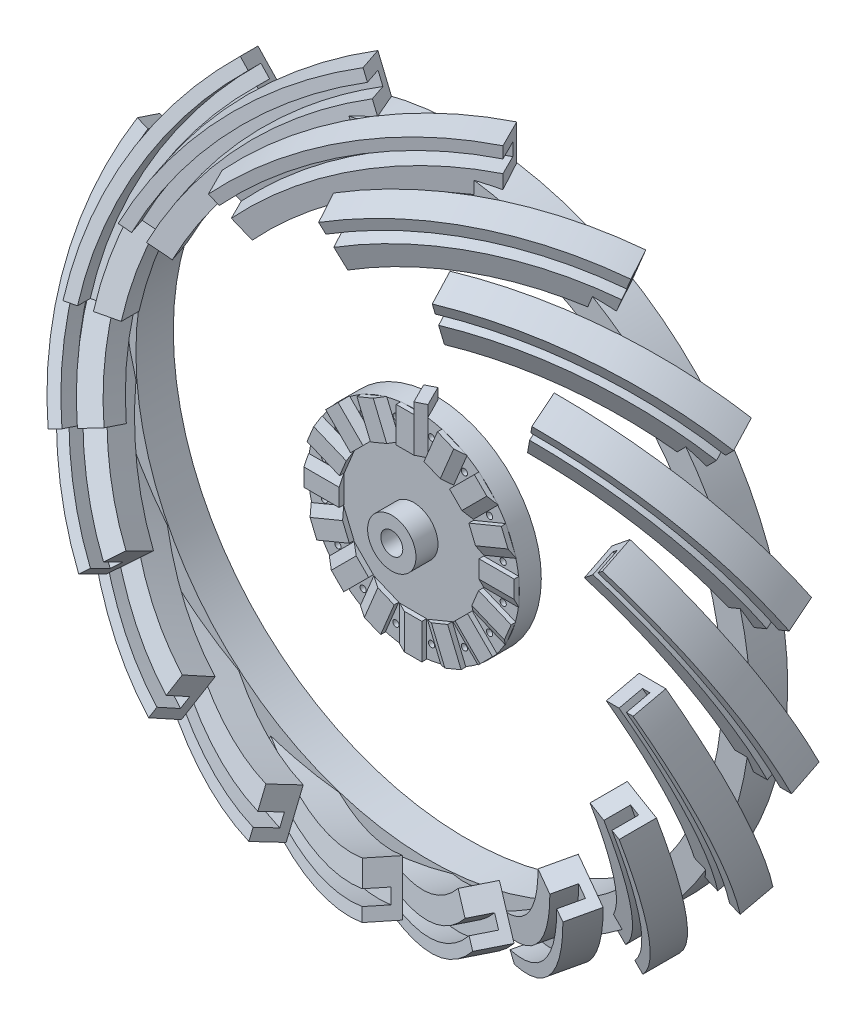
SolidWorks part; units mm, degrees
ref_plane "Front" through (0, 0, 0) normal (0, 0, 1) x (1, 0, 0)
ref_plane "Top" through (0, 0, 0) normal (0, 1, 0) x (1, 0, 0)
ref_plane "Right" through (0, 0, 0) normal (1, 0, 0) x (0, 0, -1)
sketch "Sketch1" plane through (0, 0, 0) normal (0, 0, 1) x (1, 0, 0)
  circle A0 centre (0, 0) radius 24
extrude "Extrude1" add sketch "Sketch1" along normal blind 5
sketch "Sketch2" plane through (0, 0, 5) normal (0, 0, 1) x (1, 0, 0)
  circle A0 centre (0, 0) radius 5.5
extrude "Extrude2" add sketch "Sketch2" along normal blind 5
sketch "Sketch3" plane through (0, 0, 10) normal (0, 0, 1) x (1, 0, 0)
  circle A0 centre (0, 0) radius 2.5
extrude "Cut-Extrude1" cut sketch "Sketch3" against normal through all
sketch "Sketch4" plane through (0, 0, 5) normal (0, 0, 1) x (1, 0, 0)
  circle A0 centre (0, 20.73) radius 0.7
  circle A1 centre (0, -20.73) radius 0.7
  circle A2 centre (20.73, 0) radius 0.7
  circle A3 centre (-20.73, 0) radius 0.7
  circle A4 centre (-14.658, 14.658) radius 0.7
  circle A5 centre (14.658, 14.658) radius 0.7
  circle A6 centre (14.658, -14.658) radius 0.7
  circle A7 centre (-14.658, -14.658) radius 0.7
  circle A8 centre (19.152, 7.933) radius 0.7
  circle A9 centre (7.933, 19.152) radius 0.7
  circle A10 centre (19.152, -7.933) radius 0.7
  circle A11 centre (7.933, -19.152) radius 0.7
  circle A12 centre (-7.933, 19.152) radius 0.7
  circle A13 centre (-19.152, 7.933) radius 0.7
  circle A14 centre (-19.152, -7.933) radius 0.7
  circle A15 centre (-7.933, -19.152) radius 0.7
  circle A16 centre (20.331, 4.044) radius 0.7
  circle A17 centre (20.331, -4.044) radius 0.7
  circle A18 centre (4.044, -20.331) radius 0.7
  circle A19 centre (-4.044, -20.331) radius 0.7
  circle A20 centre (4.044, 20.331) radius 0.7
  circle A21 centre (-4.044, 20.331) radius 0.6677
  circle A22 centre (-20.331, 4.044) radius 0.7
  circle A23 centre (-20.331, -4.044) radius 0.7
  circle A24 centre (17.236, 11.516) radius 0.7
  circle A25 centre (11.516, 17.236) radius 0.7
  circle A26 centre (17.236, -11.516) radius 0.7
  circle A27 centre (11.516, -17.236) radius 0.7
  circle A28 centre (-11.516, -17.236) radius 0.7
  circle A29 centre (-17.236, -11.516) radius 0.7
  circle A30 centre (-17.236, 11.516) radius 0.7
  circle A31 centre (-11.516, 17.236) radius 0.7
  circle A32 centre (0, 17.555) radius 0.7
  circle A33 centre (17.555, 0) radius 0.7
  circle A34 centre (0, -17.555) radius 0.7
  circle A35 centre (-17.555, 0) radius 0.7
  circle A36 centre (-12.413, 12.413) radius 0.7
  circle A37 centre (12.413, 12.413) radius 0.7
  circle A38 centre (12.413, -12.413) radius 0.7
  circle A39 centre (-12.413, -12.413) radius 0.7
  circle A40 centre (-16.218, 6.718) radius 0.7
  circle A41 centre (16.218, 6.718) radius 0.7
  circle A42 centre (16.218, -6.718) radius 0.7
  circle A43 centre (-16.218, -6.718) radius 0.7
  circle A44 centre (6.718, 16.218) radius 0.7
  circle A45 centre (6.718, -16.218) radius 0.7
  circle A46 centre (-6.718, -16.218) radius 0.7
  circle A47 centre (-6.718, 16.218) radius 0.7
extrude "Cut-Extrude2" cut sketch "Sketch4" against normal through all
sketch "Sketch5" plane through (0, 0, 5) normal (0, 0, 1) x (1, 0, 0)
  line L0 (0, 25.4) -> (0, 11.1125) construction
  line L1 (3.2361, 25.4) -> (3.2361, 11.1125) construction
  line L2 (-2.9131, 25.4) -> (-2.9131, 11.1125) construction
  line L3 (-6.35, 15.905) -> (6.35, 15.905) construction
  line L4 (-6.35, 23.905) -> (6.35, 23.905) construction
  line L5 (-2.9131, 23.905) -> (3.2361, 23.905)
  line L6 (3.2361, 23.905) -> (3.2361, 15.905)
  line L7 (3.2361, 15.905) -> (-2.9131, 15.905)
  line L8 (-2.9131, 15.905) -> (-2.9131, 23.905)
  line L9 (-7.933, -19.152) -> (7.933, 19.152) construction
  line L10 (6.0866, 14.6943) -> (32.5356, 3.7388) construction
  line L11 (3.3952, 15.8091) -> (7.7143, 26.2363) construction
  line L12 (9.0763, 13.4559) -> (14.7806, 27.2273) construction
  line L13 (7.5216, 22.759) -> (13.5204, 20.2742) construction
  line L14 (3.3952, 15.8091) -> (9.0763, 13.4559)
  line L15 (9.0763, 13.4559) -> (12.1378, 20.8469)
  line L16 (12.1378, 20.8469) -> (6.4566, 23.2001)
  line L17 (6.4566, 23.2001) -> (3.3952, 15.8091)
  line L18 (14.658, 14.658) -> (-14.658, -14.658) construction
  line L19 (11.2462, 11.2462) -> (25.5337, -3.0413) construction
  line L20 (13.4007, 8.8243) -> (30.8632, 26.2868) construction
  line L21 (9.0526, 13.1724) -> (26.5151, 30.6349) construction
  line L22 (14.8432, 18.963) -> (19.1913, 14.6148)
  line L23 (14.8432, 18.963) -> (9.1863, 13.3061)
  line L24 (9.1863, 13.3061) -> (13.5345, 8.958)
  line L25 (13.5345, 8.958) -> (19.1913, 14.6148)
  line L26 (19.152, 7.933) -> (-19.152, -7.933) construction
  line L27 (20.73, 0) -> (-20.73, 0) construction
  line L28 (19.152, -7.933) -> (-19.152, 7.933) construction
  line L29 (14.658, -14.658) -> (-14.658, 14.658) construction
  line L30 (-7.933, 19.152) -> (7.933, -19.152) construction
  line L31 (14.6943, 6.0866) -> (26.1, -21.4493) construction
  line L32 (15.9327, 3.0968) -> (32.1449, 9.8121) construction
  line L33 (13.5795, 8.7779) -> (25.8947, 13.8791) construction
  line L34 (20.9705, 11.8394) -> (23.3237, 6.1583)
  line L35 (20.9705, 11.8394) -> (13.5795, 8.7779)
  line L36 (13.5795, 8.7779) -> (15.9327, 3.0968)
  line L37 (15.9327, 3.0968) -> (23.3237, 6.1583)
  line L38 (15.905, 0) -> (15.905, 4.7625) construction
  line L39 (15.905, -3.2361) -> (31.8862, -3.2361) construction
  line L40 (15.905, 2.9131) -> (31.5496, 2.9131) construction
  line L41 (23.905, 2.9131) -> (23.905, -3.2361)
  line L42 (23.905, 2.9131) -> (15.905, 2.9131)
  line L43 (15.905, 2.9131) -> (15.905, -3.2361)
  line L44 (15.905, -3.2361) -> (23.905, -3.2361)
  line L45 (14.6943, -6.0866) -> (6.7144, -25.3518) construction
  line L46 (13.4559, -9.0763) -> (25.0028, -13.8592) construction
  line L47 (15.8091, -3.3952) -> (27.2231, -8.123) construction
  line L48 (23.2001, -6.4566) -> (20.8469, -12.1378)
  line L49 (23.2001, -6.4566) -> (15.8091, -3.3952)
  line L50 (15.8091, -3.3952) -> (13.4559, -9.0763)
  line L51 (13.4559, -9.0763) -> (20.8469, -12.1378)
  line L52 (11.2462, -11.2462) -> (-3.0413, -25.5337) construction
  line L53 (7.1331, -11.7096) -> (17.0531, -21.6296) construction
  line L54 (11.4812, -7.3614) -> (21.765, -17.6452) construction
  line L55 (18.963, -14.8432) -> (14.6148, -19.1913)
  line L56 (18.963, -14.8432) -> (13.3061, -9.1863)
  line L57 (13.3061, -9.1863) -> (8.958, -13.5345)
  line L58 (8.958, -13.5345) -> (14.6148, -19.1913)
  line L59 (6.0866, -14.6943) -> (0.6833, -16.9324) construction
  line L60 (8.4747, -12.8475) -> (14.1924, -26.6512) construction
  line L61 (2.7936, -15.2007) -> (8.1119, -28.0403) construction
  line L62 (6.1583, -23.3237) -> (11.8394, -20.9705)
  line L63 (11.8394, -20.9705) -> (8.7779, -13.5795)
  line L64 (8.7779, -13.5795) -> (3.0968, -15.9327)
  line L65 (3.0968, -15.9327) -> (6.1583, -23.3237)
  line L66 (0, -15.905) -> (-4.7625, -15.905) construction
  line L67 (-3.2361, -15.875) -> (-3.2361, -30.1625) construction
  line L68 (2.9131, -15.875) -> (2.9131, -31.75) construction
  line L69 (-3.2361, -23.905) -> (2.9131, -23.905)
  line L70 (-3.2361, -23.905) -> (-3.2361, -15.905)
  line L71 (-3.2361, -15.905) -> (2.9131, -15.905)
  line L72 (2.9131, -15.905) -> (2.9131, -23.905)
  line L73 (-6.0866, -14.6943) -> (-27.3638, -5.881) construction
  line L74 (-8.7952, -12.7772) -> (-13.9335, -25.1822) construction
  line L75 (-3.1239, -15.1541) -> (-9.8518, -31.3967) construction
  line L76 (-12.1378, -20.8469) -> (-6.4566, -23.2001)
  line L77 (-12.1378, -20.8469) -> (-9.0763, -13.4559)
  line L78 (-9.0763, -13.4559) -> (-3.3952, -15.8091)
  line L79 (-3.3952, -15.8091) -> (-6.4566, -23.2001)
  line L80 (-11.2462, -11.2462) -> (-14.4212, -8.0712) construction
  line L81 (-13.4007, -8.8243) -> (-22.099, -17.5225) construction
  line L82 (-9.0526, -13.1724) -> (-16.9901, -21.1099) construction
  line L83 (-19.1913, -14.6148) -> (-14.8432, -18.963)
  line L84 (-19.1913, -14.6148) -> (-13.5345, -8.958)
  line L85 (-13.5345, -8.958) -> (-9.1863, -13.3061)
  line L86 (-9.1863, -13.3061) -> (-14.8432, -18.963)
  line L87 (-14.6943, -6.0866) -> (-16.3615, -2.0616) construction
  line L88 (-15.6956, -2.9986) -> (-23.6071, -6.2757) construction
  line L89 (-13.3424, -8.6797) -> (-22.8475, -12.6169) construction
  line L90 (-23.3237, -6.1583) -> (-20.9705, -11.8394)
  line L91 (-23.3237, -6.1583) -> (-15.9327, -3.0968)
  line L92 (-15.9327, -3.0968) -> (-13.5795, -8.7779)
  line L93 (-13.5795, -8.7779) -> (-20.9705, -11.8394)
  line L94 (-15.905, 0) -> (-15.905, 4.7625) construction
  line L95 (-15.875, 3.2361) -> (-30.1625, 3.2361) construction
  line L96 (-15.875, -2.9131) -> (-30.1625, -2.9131) construction
  line L97 (-23.905, 3.2361) -> (-23.905, -2.9131)
  line L98 (-23.905, 3.2361) -> (-15.905, 3.2361)
  line L99 (-15.905, 3.2361) -> (-15.905, -2.9131)
  line L100 (-15.905, -2.9131) -> (-23.905, -2.9131)
  line L101 (-14.6943, 6.0866) -> (-12.6964, 10.9098) construction
  line L102 (-12.6129, 8.7271) -> (-24.5831, 13.6853) construction
  line L103 (-14.9661, 3.046) -> (-23.8286, 6.717) construction
  line L104 (-20.8469, 12.1378) -> (-23.2001, 6.4566)
  line L105 (-20.8469, 12.1378) -> (-13.4559, 9.0763)
  line L106 (-13.4559, 9.0763) -> (-15.8091, 3.3952)
  line L107 (-15.8091, 3.3952) -> (-23.2001, 6.4566)
  line L108 (-11.2462, 11.2462) -> (-8.0712, 14.4212) construction
  line L109 (-8.8243, 13.4007) -> (-15.1743, 19.7507) construction
  line L110 (-13.1724, 9.0526) -> (-21.1099, 16.9901) construction
  line L111 (-14.6148, 19.1913) -> (-18.963, 14.8432)
  line L112 (-14.6148, 19.1913) -> (-8.958, 13.5345)
  line L113 (-8.958, 13.5345) -> (-13.3061, 9.1863)
  line L114 (-13.3061, 9.1863) -> (-18.963, 14.8432)
  line L115 (-6.0866, 14.6943) -> (-4.1884, 15.4805) construction
  line L116 (-2.9779, 15.6455) -> (-5.3968, 21.4853) construction
  line L117 (-8.659, 13.2923) -> (-12.5274, 22.6316) construction
  line L118 (-11.8394, 20.9705) -> (-6.1583, 23.3237)
  line L119 (-6.1583, 23.3237) -> (-3.0968, 15.9327)
  line L120 (-3.0968, 15.9327) -> (-8.7779, 13.5795)
  line L121 (-8.7779, 13.5795) -> (-11.8394, 20.9705)
  point P11 (0, 20.73)
  point P22 (6.0866, 14.6943)
  point P36 (11.2462, 11.2462)
  point P43 (7.933, 19.152)
  point P45 (14.658, 14.658)
  point P47 (19.152, 7.933)
  point P61 (20.73, 0)
  point P65 (19.152, -7.933)
  point P67 (14.658, -14.658)
  point P69 (7.933, -19.152)
  point P71 (0, -20.73)
  point P73 (-7.933, -19.152)
  point P75 (-14.658, -14.658)
  point P77 (-19.152, -7.933)
  point P79 (-20.73, 0)
  point P81 (-19.152, 7.933)
  point P83 (-14.658, 14.658)
  point P85 (-7.933, 19.152)
  dimension "D1" = 3.2361
  dimension "D2" = 2.9131
  dimension "D3" = 3.175
  dimension "D4" = 4.825
  dimension "D5" = 4.825
  dimension "D6" = 3.175
  dimension "D7" = 3.2361
  dimension "D8" = 2.9131
  dimension "D9" = 4.825
  dimension "D10" = 3.2361
  dimension "D11" = 2.9131
  dimension "D12" = 3.175
  dimension "D13" = 4.825
  dimension "D14" = 3.2361
  dimension "D15" = 2.9131
  dimension "D16" = 3.175
  dimension "D17" = 4.825
  dimension "D18" = 3.2361
  dimension "D19" = 2.9131
  dimension "D20" = 3.175
  dimension "D21" = 4.825
  dimension "D22" = 3.2361
  dimension "D23" = 2.9131
  dimension "D24" = 3.175
  dimension "D25" = 4.825
  dimension "D26" = 3.175
  dimension "D27" = 3.2361
  dimension "D28" = 2.9131
  dimension "D29" = 4.825
  dimension "D30" = 2.9131
  dimension "D31" = 3.2361
  dimension "D32" = 3.175
  dimension "D33" = 3.2361
  dimension "D34" = 2.9131
  dimension "D35" = 3.175
  dimension "D36" = 4.825
  dimension "D37" = 4.825
  dimension "D38" = 3.2361
  dimension "D39" = 2.9131
  dimension "D40" = 3.175
  dimension "D41" = 4.825
  dimension "D42" = 3.2361
  dimension "D43" = 2.9131
  dimension "D44" = 3.175
  dimension "D45" = 4.825
  dimension "D46" = 3.2361
  dimension "D47" = 2.9131
  dimension "D48" = 3.175
  dimension "D49" = 4.825
  dimension "D50" = 3.2361
  dimension "D51" = 2.9131
  dimension "D52" = 3.175
  dimension "D53" = 4.825
  dimension "D54" = 3.2361
  dimension "D55" = 2.9131
  dimension "D56" = 3.175
  dimension "D57" = 4.825
  dimension "D58" = 3.2361
  dimension "D59" = 2.9131
  dimension "D60" = 3.175
  dimension "D61" = 4.825
  dimension "D62" = 3.2361
  dimension "D63" = 2.9131
  dimension "D64" = 3.175
extrude "Extrude4" add sketch "Sketch5" along normal blind 1.0733
sketch "Sketch6" plane through (0, 23.905, 0) normal (0, 1, 0) x (1, 0, 0)
  line L0 (3.2361, -6.0733) -> (-2.9131, -6.0733) construction
  line L1 (3.2361, -6.0733) -> (3.2361, -5) construction
  line L2 (1.0894, -6.0733) -> (3.2361, -5)
  line L3 (3.2361, -5) -> (3.2361, -6.0733)
  line L4 (3.2361, -6.0733) -> (1.0894, -6.0733)
  point P0 (1.0894, -6.0733)
  dimension "D1" = 2.1466
extrude "Extrude5" cut sketch "Sketch6" against normal up to surface (8 mm away) up to face at (0.1615, 15.905, 5.5367)
sketch "Sketch7" plane through (2.6472, 0, 5.2944) normal (0.4472, 0, 0.8944) x (0.8944, 0, -0.4472)
  line L0 (0.6584, 23.905) -> (-1.7416, 23.905)
  line L1 (-1.7416, 23.905) -> (-1.7416, 26.405)
  line L2 (0.6584, 23.905) -> (0.6584, 26.405)
  line L3 (0.6584, 26.405) -> (-1.7416, 26.405)
extrude "Extrude6" add sketch "Sketch7" against normal blind 5
sketch "Sketch9" plane through (9.148, 22.0853, 0) normal (0.3827, 0.9239, 0) x (0.9239, -0.3827, 0)
  line L0 (3.2361, -6.0733) -> (-2.9131, -6.0733) construction
  line L1 (3.2361, -6.0733) -> (3.2361, -5) construction
  line L2 (1.0894, -6.0733) -> (3.2361, -5)
  line L3 (3.2361, -5) -> (3.2361, -6.0733)
  line L4 (3.2361, -6.0733) -> (1.0894, -6.0733)
  point P0 (1.0894, -6.0733)
  dimension "D1" = 2.1466
extrude "Extrude7" cut sketch "Sketch9" against normal up to surface (8 mm away) up to face at (6.2357, 14.6325, 5.5367)
sketch "Sketch10" plane through (16.9031, 16.9031, 0) normal (0.7071, 0.7071, 0) x (0, 0, -1)
  line L0 (-6.0733, -3.2361) -> (-6.0733, 2.9131) construction
  line L1 (-6.0733, -3.2361) -> (-5, -3.2361) construction
  line L2 (-6.0733, -1.0894) -> (-5, -3.2361)
  line L3 (-5, -3.2361) -> (-6.0733, -3.2361)
  line L4 (-6.0733, -3.2361) -> (-6.0733, -1.0894)
  point P0 (-6.0733, -1.0894)
  dimension "D1" = 2.1466
extrude "Extrude8" cut sketch "Sketch10" against normal up to surface (8 mm away) up to face at (11.3604, 11.132, 5.5367)
sketch "Sketch11" plane through (22.0853, 9.148, 0) normal (0.9239, 0.3827, 0) x (0, 0, -1)
  line L0 (-6.0733, -3.2361) -> (-6.0733, 2.9131) construction
  line L1 (-6.0733, -3.2361) -> (-5, -3.2361) construction
  line L2 (-6.0733, -1.0894) -> (-5, -3.2361)
  line L3 (-5, -3.2361) -> (-6.0733, -3.2361)
  line L4 (-6.0733, -3.2361) -> (-6.0733, -1.0894)
  point P0 (-6.0733, -1.0894)
  dimension "D1" = 2.1466
extrude "Extrude9" cut sketch "Sketch11" against normal up to surface (8 mm away) up to face at (14.7561, 5.9374, 5.5367)
sketch "Sketch12" plane through (23.905, 0, 0) normal (1, 0, 0) x (0, 0, -1)
  line L0 (-6.0733, -3.2361) -> (-6.0733, 2.9131) construction
  line L1 (-6.0733, -3.2361) -> (-5, -3.2361) construction
  line L2 (-6.0733, -1.0894) -> (-5, -3.2361)
  line L3 (-5, -3.2361) -> (-6.0733, -3.2361)
  line L4 (-6.0733, -3.2361) -> (-6.0733, -1.0894)
  point P0 (-6.0733, -1.0894)
  dimension "D1" = 2.1466
extrude "Extrude10" cut sketch "Sketch12" against normal up to surface (8 mm away) up to face at (15.905, -0.1615, 5.5367)
sketch "Sketch13" plane through (22.0853, -9.148, 0) normal (0.9239, -0.3827, 0) x (0, 0, -1)
  line L0 (-6.0733, -3.2361) -> (-6.0733, 2.9131) construction
  line L1 (-6.0733, -3.2361) -> (-5, -3.2361) construction
  line L2 (-6.0733, -1.0894) -> (-5, -3.2361)
  line L3 (-5, -3.2361) -> (-6.0733, -3.2361)
  line L4 (-6.0733, -3.2361) -> (-6.0733, -1.0894)
  point P0 (-6.0733, -1.0894)
  dimension "D1" = 2.1466
extrude "Extrude11" cut sketch "Sketch13" against normal up to surface (8 mm away) up to face at (14.6325, -6.2357, 5.5367)
sketch "Sketch14" plane through (16.9031, -16.9031, 0) normal (0.7071, -0.7071, 0) x (0, 0, -1)
  line L0 (-6.0733, -3.2361) -> (-6.0733, 2.9131) construction
  line L1 (-6.0733, -3.2361) -> (-5, -3.2361) construction
  line L2 (-6.0733, -1.0894) -> (-5, -3.2361)
  line L3 (-5, -3.2361) -> (-6.0733, -3.2361)
  line L4 (-6.0733, -3.2361) -> (-6.0733, -1.0894)
  point P0 (-6.0733, -1.0894)
  dimension "D1" = 2.1466
extrude "Extrude12" cut sketch "Sketch14" against normal up to surface (8 mm away) up to face at (11.132, -11.3604, 5.5367)
sketch "Sketch15" plane through (9.148, -22.0853, 0) normal (0.3827, -0.9239, 0) x (0.9239, 0.3827, 0)
  line L0 (-3.2361, 6.0733) -> (2.9131, 6.0733) construction
  line L1 (-3.2361, 6.0733) -> (-3.2361, 5) construction
  line L2 (-1.0894, 6.0733) -> (-3.2361, 5)
  line L3 (-3.2361, 5) -> (-3.2361, 6.0733)
  line L4 (-3.2361, 6.0733) -> (-1.0894, 6.0733)
  point P0 (-1.0894, 6.0733)
  dimension "D1" = 2.1466
extrude "Extrude13" cut sketch "Sketch15" against normal up to surface (8 mm away) up to face at (5.9374, -14.7561, 5.5367)
sketch "Sketch16" plane through (0, -23.905, 0) normal (0, -1, 0) x (1, 0, 0)
  line L0 (-3.2361, 6.0733) -> (2.9131, 6.0733) construction
  line L1 (-3.2361, 6.0733) -> (-3.2361, 5) construction
  line L2 (-1.0894, 6.0733) -> (-3.2361, 5)
  line L3 (-3.2361, 5) -> (-3.2361, 6.0733)
  line L4 (-3.2361, 6.0733) -> (-1.0894, 6.0733)
  point P0 (-1.0894, 6.0733)
  dimension "D1" = 2.1466
extrude "Extrude14" cut sketch "Sketch16" against normal up to surface (8 mm away) up to face at (-0.1615, -15.905, 5.5367)
sketch "Sketch17" plane through (-9.148, -22.0853, 0) normal (-0.3827, -0.9239, 0) x (0.9239, -0.3827, 0)
  line L0 (-3.2361, 6.0733) -> (2.9131, 6.0733) construction
  line L1 (-3.2361, 6.0733) -> (-3.2361, 5) construction
  line L2 (-1.0894, 6.0733) -> (-3.2361, 5)
  line L3 (-3.2361, 5) -> (-3.2361, 6.0733)
  line L4 (-3.2361, 6.0733) -> (-1.0894, 6.0733)
  point P0 (-1.0894, 6.0733)
  dimension "D1" = 2.1466
extrude "Extrude15" cut sketch "Sketch17" against normal up to surface (8 mm away) up to face at (-6.2357, -14.6325, 5.5367)
sketch "Sketch18" plane through (-16.9031, -16.9031, 0) normal (-0.7071, -0.7071, 0) x (0, 0, 1)
  line L0 (6.0733, 3.2361) -> (6.0733, -2.9131) construction
  line L1 (6.0733, 3.2361) -> (5, 3.2361) construction
  line L2 (6.0733, 1.0894) -> (5, 3.2361)
  line L3 (5, 3.2361) -> (6.0733, 3.2361)
  line L4 (6.0733, 3.2361) -> (6.0733, 1.0894)
  point P0 (6.0733, 1.0894)
  dimension "D1" = 2.1466
extrude "Extrude16" cut sketch "Sketch18" against normal up to surface (8 mm away) up to face at (-11.3604, -11.132, 5.5367)
sketch "Sketch19" plane through (-22.0853, -9.148, 0) normal (-0.9239, -0.3827, 0) x (0, 0, 1)
  line L0 (6.0733, 3.2361) -> (6.0733, -2.9131) construction
  line L1 (6.0733, 3.2361) -> (5, 3.2361) construction
  line L2 (6.0733, 1.0894) -> (5, 3.2361)
  line L3 (5, 3.2361) -> (6.0733, 3.2361)
  line L4 (6.0733, 3.2361) -> (6.0733, 1.0894)
  point P0 (6.0733, 1.0894)
  dimension "D1" = 2.1466
extrude "Extrude17" cut sketch "Sketch19" against normal up to surface (8 mm away) up to face at (-14.7561, -5.9374, 5.5367)
sketch "Sketch20" plane through (-23.905, 0, 0) normal (-1, 0, 0) x (0, 0, 1)
  line L0 (6.0733, 3.2361) -> (6.0733, -2.9131) construction
  line L1 (6.0733, 3.2361) -> (5, 3.2361) construction
  line L2 (6.0733, 1.0894) -> (5, 3.2361)
  line L3 (5, -5.5) -> (5, 5.5) construction
  line L4 (5, 3.2361) -> (6.0733, 3.2361)
  line L5 (6.0733, 3.2361) -> (6.0733, 1.0894)
  point P0 (6.0733, 1.0894)
  dimension "D1" = 2.1466
extrude "Extrude18" cut sketch "Sketch20" against normal up to surface (8 mm away) up to face at (-15.905, 0.1615, 5.5367)
sketch "Sketch21" plane through (-22.0853, 9.148, 0) normal (-0.9239, 0.3827, 0) x (0, 0, 1)
  line L0 (6.0733, 3.2361) -> (6.0733, -2.9131) construction
  line L1 (6.0733, 3.2361) -> (5, 3.2361) construction
  line L2 (6.0733, 1.0894) -> (5, 3.2361)
  line L3 (5, 3.2361) -> (6.0733, 3.2361)
  line L4 (6.0733, 3.2361) -> (6.0733, 1.0894)
  point P1 (6.0733, 1.0894)
  dimension "D1" = 2.1466
extrude "Extrude19" cut sketch "Sketch21" against normal up to surface (8 mm away) up to face at (-14.6325, 6.2357, 5.5367)
sketch "Sketch22" plane through (-16.9031, 16.9031, 0) normal (-0.7071, 0.7071, 0) x (0, 0, 1)
  line L0 (6.0733, 3.2361) -> (6.0733, -2.9131) construction
  line L1 (6.0733, 3.2361) -> (5, 3.2361) construction
  line L2 (6.0733, 1.0894) -> (5, 3.2361)
  line L3 (5, 3.2361) -> (6.0733, 3.2361)
  line L4 (6.0733, 3.2361) -> (6.0733, 1.0894)
  point P0 (6.0733, 1.0894)
  dimension "D1" = 2.1466
extrude "Extrude20" cut sketch "Sketch22" against normal up to surface (8 mm away) up to face at (-11.132, 11.3604, 5.5367)
sketch "Sketch23" plane through (-9.148, 22.0853, 0) normal (-0.3827, 0.9239, 0) x (0.9239, 0.3827, 0)
  line L0 (3.2361, -6.0733) -> (-2.9131, -6.0733) construction
  line L1 (3.2361, -6.0733) -> (3.2361, -5) construction
  line L2 (1.0894, -6.0733) -> (3.2361, -5)
  line L3 (3.2361, -5) -> (3.2361, -6.0733)
  line L4 (3.2361, -6.0733) -> (1.0894, -6.0733)
  point P0 (1.0894, -6.0733)
  dimension "D1" = 2.1466
extrude "Extrude21" cut sketch "Sketch23" against normal up to surface (8 mm away) up to face at (-5.9374, 14.7561, 5.5367)
sketch "Sketch24" plane through (2.6472, 0, 5.2944) normal (0.4472, 0, 0.8944) x (0.8944, 0, -0.4472)
  line L0 (0.6658, 23.9161) -> (0.6584, 17.0853) construction
  line L2 (-38.7315, 23.905) -> (-26.3758, 23.905) construction
  line L3 (0.6584, 9.6175) -> (45.4529, 9.6175) construction
  line L4 (13.3584, 23.905) -> (13.3584, 11.462) construction
  line L5 (13.3584, 9.6175) -> (-32.6655, 55.6413) construction
  line L6 (-34.7161, 57.6919) -> (-36.5545, 59.5304)
  line L7 (13.3584, 77.605) -> (13.3584, 80.205)
  line L8 (13.3584, 74.705) -> (13.3584, 69.705)
  line L9 (-29.1299, 52.1058) -> (-32.6655, 55.6413)
  arc A0 (-51.7291, 9.6175) -> (13.3584, 74.705) centre (13.3584, 9.6175) cw construction
  arc A1 (-29.1299, 52.1058) -> (13.3584, 69.705) centre (13.3584, 9.6175) cw
  arc A2 (-32.6655, 55.6413) -> (13.3584, 74.705) centre (13.3584, 9.6175) cw
  arc A3 (-34.7161, 57.6919) -> (13.3584, 77.605) centre (13.3584, 9.6175) cw
  arc A4 (-36.5545, 59.5304) -> (13.3584, 80.205) centre (13.3584, 9.6175) cw
  point P1 (0.6584, 23.905)
  point P4 (13.3584, 9.6175)
  dimension "D3" = 65.0875
  dimension "D1" = 14.2875
  dimension "D2" = 12.7
extrude "Extrude22" add sketch "Sketch24" against normal blind 5 separate body
sketch "Sketch25" plane through (2.4457, -1.013, 5.2944) normal (0.4132, -0.1711, 0.8944) x (0.9107, 0.0776, -0.4058)
  line L0 (10.3024, 21.5728) -> (7.7047, 15.9634) construction
  line L1 (-42.8961, 30.4641) -> (-45.5276, 31.6827) construction
  line L2 (10.643, 21.4151) -> (8.4652, 22.4237) construction
  line L3 (4.6389, 8.4504) -> (17.1409, 2.6607) construction
  line L4 (3.8691, -22.5406) -> (18.518, 9.0914) construction
  line L5 (16.1654, 3.1124) -> (-6.2578, 64.2155) construction
  line L6 (43.1738, 62.3318) -> (41.0726, 57.7946)
  line L7 (45.4851, 67.3227) -> (44.3925, 64.9633)
  line L8 (-8.1526, 69.3788) -> (-7.2569, 66.9379)
  line L9 (-4.5353, 59.5215) -> (-6.2578, 64.2155)
  arc A0 (-45.5276, 31.6827) -> (44.3925, 64.9633) centre (16.1654, 3.1124) cw construction
  arc A1 (-42.8961, 30.4641) -> (43.1738, 62.3318) centre (16.1654, 3.1124) cw construction
  arc A2 (-4.5353, 59.5215) -> (41.0726, 57.7946) centre (16.1654, 3.1124) cw
  arc A3 (45.4851, 67.3227) -> (-8.1526, 69.3788) centre (16.1654, 3.1124) ccw
  arc A4 (43.1738, 62.3318) -> (-6.2578, 64.2155) centre (16.1654, 3.1124) ccw
  arc A5 (-7.2569, 66.9379) -> (44.3925, 64.9633) centre (16.1654, 3.1124) cw
  point P2 (4.2984, 8.6081)
  point P3 (10.643, 21.4151)
  point P7 (16.1654, 3.1124)
  dimension "D3" = 65.0875
  dimension "D4" = 67.9875
  dimension "D1" = 14.2875
  dimension "D2" = 12.7
extrude "Extrude24" add sketch "Sketch25" against normal blind 5 separate body
sketch "Sketch26" plane through (1.8719, -1.8719, 5.2944) normal (0.3162, -0.3162, 0.8944) x (0.9487, 0.1054, -0.2981)
  line L0 (18.2563, 15.4456) -> (13.3855, 11.0891) construction
  line L2 (18.2563, 15.4456) -> (16.8993, 16.9628) construction
  line L4 (7.607, 5.9206) -> (26.9904, -15.7506) construction
  line L5 (16.0737, -3.5454) -> (40.6268, 18.4156) construction
  line L6 (16.0737, -3.5454) -> (19.6953, 61.4413) construction
  line L7 (19.4171, 56.449) -> (19.6953, 61.4413)
  line L8 (60.8603, 36.513) -> (64.5871, 39.8463)
  line L9 (66.7486, 41.7796) -> (68.6865, 43.513)
  line L10 (19.8566, 64.3368) -> (20.0013, 66.9328)
  arc A0 (-27.318, 44.968) -> (64.5871, 39.8463) centre (16.0737, -3.5454) cw construction
  arc A1 (66.7486, 41.7796) -> (-29.2513, 47.1295) centre (16.0737, -3.5454) ccw construction
  arc A2 (60.8603, 36.513) -> (19.4171, 56.449) centre (16.0737, -3.5454) ccw
  arc A3 (68.6865, 43.513) -> (20.0013, 66.9328) centre (16.0737, -3.5454) ccw
  arc A4 (64.5871, 39.8463) -> (19.6953, 61.4413) centre (16.0737, -3.5454) ccw
  arc A5 (66.7486, 41.7796) -> (19.8566, 64.3368) centre (16.0737, -3.5454) ccw
  point P1 (18.2563, 15.4456)
  point P10 (16.0737, -3.5454)
  dimension "D3" = 65.0875
  dimension "D4" = 67.9875
  dimension "D1" = 14.2875
  dimension "D2" = 12.7
extrude "Extrude25" add sketch "Sketch26" against normal blind 5 separate body
sketch "Sketch27" plane through (1.013, -2.4457, 5.2944) normal (0.1711, -0.4132, 0.8944) x (0.9852, 0.0718, -0.1554)
  line L0 (22.6448, 7.6874) -> (20.4937, 6.8905) construction
  line L1 (27.0568, -4.2216) -> (-11.9723, -18.6812) construction
  line L2 (20.4617, 13.5798) -> (20.2208, 14.2302) construction
  line L3 (13.6592, -9.1851) -> (40.8274, 49.961) construction
  line L4 (9.2472, 2.7238) -> (19.0095, -23.6265) construction
  line L5 (70.0041, 11.6897) -> (74.6927, 13.4267)
  line L6 (77.4121, 14.4342) -> (79.8501, 15.3375)
  line L7 (38.7404, 45.4175) -> (40.8274, 49.961)
  line L8 (42.0379, 52.5963) -> (43.1232, 54.959)
  arc A0 (-8.9526, 51.8483) -> (74.6927, 13.4267) centre (13.6592, -9.1851) cw construction
  arc A1 (77.4121, 14.4342) -> (42.0379, 52.5963) centre (13.6592, -9.1851) ccw
  arc A2 (79.8501, 15.3375) -> (43.1232, 54.959) centre (13.6592, -9.1851) ccw
  arc A3 (70.0041, 11.6897) -> (38.7404, 45.4175) centre (13.6592, -9.1851) ccw
  arc A4 (74.6927, 13.4267) -> (40.8274, 49.961) centre (13.6592, -9.1851) ccw
  point P0 (22.6448, 7.6874)
  point P4 (25.1428, 0.9448)
  point P9 (13.6592, -9.1851)
  dimension "D3" = 65.0875
  dimension "D4" = 67.9875
  dimension "D1" = 14.2875
  dimension "D2" = 12.7
extrude "Extrude26" add sketch "Sketch27" against normal blind 5 separate body
sketch "Sketch28" plane through (0, -2.6472, 5.2944) normal (0, -0.4472, 0.8944) x (1, 0, 0)
  line L0 (23.905, -0.6584) -> (17.5467, -0.6584) construction
  line L2 (23.905, -0.6584) -> (23.905, 4.4943) construction
  line L4 (9.6175, -0.6584) -> (9.6175, -21.4145) construction
  line L5 (23.905, -13.3584) -> (-24.4071, -13.3584) construction
  line L6 (9.6175, -13.3584) -> (55.6413, 32.6655) construction
  line L7 (52.1058, 29.1299) -> (55.6413, 32.6655)
  line L8 (69.705, -13.3584) -> (74.705, -13.3584)
  line L9 (77.605, -13.3584) -> (80.205, -13.3584)
  line L10 (57.6919, 34.7161) -> (59.5304, 36.5545)
  arc A0 (9.6175, 51.7291) -> (74.705, -13.3584) centre (9.6175, -13.3584) cw construction
  arc A1 (69.705, -13.3584) -> (52.1058, 29.1299) centre (9.6175, -13.3584) ccw
  arc A2 (74.705, -13.3584) -> (55.6413, 32.6655) centre (9.6175, -13.3584) ccw
  arc A3 (77.605, -13.3584) -> (57.6919, 34.7161) centre (9.6175, -13.3584) ccw
  arc A4 (80.205, -13.3584) -> (59.5304, 36.5545) centre (9.6175, -13.3584) ccw
  point P0 (23.905, -0.6584)
  point P9 (9.6175, -13.3584)
  dimension "D3" = 65.0875
  dimension "D1" = 14.2875
  dimension "D2" = 12.7
extrude "Extrude27" add sketch "Sketch28" against normal blind 5 separate body
sketch "Sketch29" plane through (-1.013, -2.4457, 5.2944) normal (-0.1711, -0.4132, 0.8944) x (0.9852, -0.0718, 0.1554)
  line L0 (22.1873, -8.9221) -> (22.8584, -7.1106) construction
  line L2 (22.1873, -8.9221) -> (17.6186, -7.2295) construction
  line L4 (8.7897, -3.9585) -> (-0.5909, -29.2786) construction
  line L5 (4.3776, -15.8675) -> (20.4597, -21.8256) construction
  line L6 (4.3776, -15.8675) -> (63.5238, 11.3007) construction
  line L7 (58.9803, 9.2136) -> (63.5238, 11.3007)
  line L8 (66.1591, 12.5112) -> (68.5218, 13.5964)
  line L9 (60.7226, -36.7423) -> (65.4111, -38.4794)
  line L10 (68.1305, -39.4869) -> (70.5686, -40.3901)
  arc A0 (65.4111, -38.4794) -> (26.9895, 45.166) centre (4.3776, -15.8675) ccw construction
  arc A1 (63.5238, 11.3007) -> (65.4111, -38.4794) centre (4.3776, -15.8675) cw
  arc A2 (58.9803, 9.2136) -> (60.7226, -36.7423) centre (4.3776, -15.8675) cw
  arc A3 (66.1591, 12.5112) -> (68.1305, -39.4869) centre (4.3776, -15.8675) cw
  arc A4 (68.5218, 13.5964) -> (70.5686, -40.3901) centre (4.3776, -15.8675) cw
  point P0 (22.1873, -8.9221)
  point P9 (4.3776, -15.8675)
  dimension "D3" = 65.0875
  dimension "D1" = 14.2875
  dimension "D2" = 12.7
extrude "Extrude28" add sketch "Sketch29" against normal blind 5 separate body
sketch "Sketch30" plane through (-1.8719, -1.8719, 5.2944) normal (-0.3162, -0.3162, 0.8944) x (0.9487, -0.1054, 0.2981)
  line L0 (17.3785, -16.4271) -> (13.5568, -13.0089) construction
  line L2 (17.3785, -16.4271) -> (19.1497, -14.4468) construction
  line L4 (6.7292, -6.9021) -> (-20.6795, -37.546) construction
  line L5 (8.9118, -25.8931) -> (-21.3759, 1.197) construction
  line L6 (-1.7375, -16.3681) -> (63.2492, -12.7465) construction
  line L7 (58.257, -13.0247) -> (63.2492, -12.7465)
  line L8 (66.1447, -12.5852) -> (68.7407, -12.4405)
  line L9 (43.0491, -56.4264) -> (46.7759, -59.7598)
  line L10 (48.9374, -61.6931) -> (50.8754, -63.4264)
  arc A0 (41.6542, 32.1453) -> (46.7759, -59.7598) centre (-1.7375, -16.3681) cw construction
  arc A1 (58.257, -13.0247) -> (43.0491, -56.4264) centre (-1.7375, -16.3681) cw
  arc A2 (46.7759, -59.7598) -> (63.2492, -12.7465) centre (-1.7375, -16.3681) ccw
  arc A3 (48.9374, -61.6931) -> (66.1447, -12.5852) centre (-1.7375, -16.3681) ccw
  arc A4 (68.7407, -12.4405) -> (50.8754, -63.4264) centre (-1.7375, -16.3681) cw
  point P0 (17.3785, -16.4271)
  point P9 (-1.7375, -16.3681)
  dimension "D3" = 65.0875
  dimension "D1" = 14.2875
  dimension "D2" = 12.7
extrude "Extrude29" add sketch "Sketch30" against normal blind 5 separate body
sketch "Sketch31" plane through (-2.4457, -1.013, 5.2944) normal (-0.4132, -0.1711, 0.8944) x (0.9107, -0.0776, 0.4058)
  line L0 (11.9977, -20.7878) -> (14.9471, -19.4219) construction
  line L2 (9.4481, -21.9685) -> (7.5816, -17.938) construction
  line L4 (3.4441, -9.0037) -> (-2.924, -11.9528) construction
  line L5 (-2.0761, -27.3054) -> (-4.6525, -21.742) construction
  line L6 (-8.0801, -14.3406) -> (53.0233, -36.7629) construction
  line L7 (48.3294, -35.0405) -> (53.0233, -36.7629)
  line L8 (55.7458, -37.762) -> (58.1866, -38.6577)
  line L9 (17.1704, -68.8651) -> (19.2716, -73.4022)
  line L10 (20.4902, -76.0337) -> (21.5828, -78.393)
  arc A0 (50.9815, 13.011) -> (19.2716, -73.4022) centre (-8.0801, -14.3406) cw construction
  arc A1 (48.3294, -35.0405) -> (17.1704, -68.8651) centre (-8.0801, -14.3406) cw
  arc A2 (50.9815, 13.011) -> (19.2716, -73.4022) centre (-8.0801, -14.3406) cw construction
  arc A3 (19.2716, -73.4022) -> (53.0233, -36.7629) centre (-8.0801, -14.3406) ccw
  arc A4 (20.4902, -76.0337) -> (55.7458, -37.762) centre (-8.0801, -14.3406) ccw
  arc A5 (21.5828, -78.393) -> (58.1866, -38.6577) centre (-8.0801, -14.3406) ccw
  point P0 (9.4481, -21.9685)
  point P9 (-8.0801, -14.3406)
  dimension "D3" = 65.0875
  dimension "D1" = 14.2875
  dimension "D2" = 12.7
extrude "Extrude30" add sketch "Sketch31" against normal blind 5 separate body
sketch "Sketch32" plane through (-2.6472, 0, 5.2944) normal (-0.4472, 0, 0.8944) x (0.8944, 0, 0.4472)
  line L0 (8.1867, -23.905) -> (10.914, -23.905) construction
  line L2 (-0.6584, -23.905) -> (-0.6584, -21.6642) construction
  line L4 (-0.6584, -9.6175) -> (-47.9479, -9.6175) construction
  line L5 (-13.3584, -23.905) -> (-13.3584, -17.8297) construction
  line L6 (-13.3584, -9.6175) -> (32.6655, -55.6413) construction
  line L7 (-13.3584, -74.705) -> (-13.3584, -69.705)
  line L8 (-13.3584, -77.605) -> (-13.3584, -80.205)
  line L9 (34.7161, -57.6919) -> (36.5545, -59.5304)
  line L10 (29.1299, -52.1058) -> (32.6655, -55.6413)
  arc A0 (51.7291, -9.6175) -> (-13.3584, -74.705) centre (-13.3584, -9.6175) cw construction
  arc A1 (29.1299, -52.1058) -> (-13.3584, -69.705) centre (-13.3584, -9.6175) cw
  arc A2 (32.6655, -55.6413) -> (-13.3584, -74.705) centre (-13.3584, -9.6175) cw
  arc A3 (34.7161, -57.6919) -> (-13.3584, -77.605) centre (-13.3584, -9.6175) cw
  arc A4 (36.5545, -59.5304) -> (-13.3584, -80.205) centre (-13.3584, -9.6175) cw
  point P0 (-0.6584, -23.905)
  point P9 (-13.3584, -9.6175)
  dimension "D3" = 65.0875
  dimension "D1" = 14.2875
  dimension "D2" = 12.7
extrude "Extrude31" add sketch "Sketch32" against normal blind 5 separate body
sketch "Sketch33" plane through (-2.4457, 1.013, 5.2944) normal (-0.4132, 0.1711, 0.8944) x (0.9107, 0.0776, 0.4058)
  line L0 (-0.2748, -26.2167) -> (2.496, -27.4999) construction
  line L2 (-10.643, -21.4151) -> (-9.525, -19.05) construction
  line L3 (-4.5372, -8.498) -> (0.4297, -10.8458) construction
  line L4 (-22.1672, -16.0782) -> (-18.2066, -7.5259) construction
  line L5 (-16.121, -3.0225) -> (6.1371, -64.1859) construction
  line L6 (-41.3715, -57.547) -> (-43.4727, -62.0841)
  line L7 (6.1371, -64.1859) -> (4.4273, -59.4873)
  line L8 (-44.6913, -64.7156) -> (-45.7839, -67.0749)
  line L9 (7.1288, -66.9111) -> (8.018, -69.3543)
  arc A0 (42.7928, -30.691) -> (-43.4727, -62.0841) centre (-16.121, -3.0225) cw construction
  arc A1 (4.4273, -59.4873) -> (-41.3715, -57.547) centre (-16.121, -3.0225) cw
  arc A2 (-43.4727, -62.0841) -> (6.1371, -64.1859) centre (-16.121, -3.0225) ccw
  arc A3 (7.1288, -66.9111) -> (-44.6913, -64.7156) centre (-16.121, -3.0225) cw
  arc A4 (8.018, -69.3543) -> (-45.7839, -67.0749) centre (-16.121, -3.0225) cw
  point P0 (-10.643, -21.4151)
  point P9 (-16.121, -3.0225)
  dimension "D3" = 65.0875
  dimension "D1" = 14.2875
  dimension "D2" = 12.7
extrude "Extrude32" add sketch "Sketch33" against normal blind 5 separate body
sketch "Sketch34" plane through (-1.8719, 1.8719, 5.2944) normal (-0.3162, 0.3162, 0.8944) x (0.9487, 0.1054, 0.2981)
  line L0 (-12.3925, -22.0016) -> (-8.8001, -26.018) construction
  line L2 (-18.2563, -15.4456) -> (-18.0754, -15.2839) construction
  line L4 (-7.607, -5.9206) -> (-1.2848, -12.9891) construction
  line L5 (-26.723, -5.9796) -> (-17.2692, 2.4761) construction
  line L6 (-16.0737, 3.5454) -> (-19.6953, -61.4413) construction
  line L7 (-68.6865, -43.513) -> (-66.7486, -41.7796)
  line L8 (-19.8566, -64.3368) -> (-20.0013, -66.9328)
  line L9 (-64.5871, -39.8463) -> (-60.8603, -36.513)
  line L10 (-19.4171, -56.449) -> (-19.6953, -61.4413)
  arc A0 (27.318, -44.968) -> (-64.5871, -39.8463) centre (-16.0737, 3.5454) cw construction
  arc A1 (-19.4171, -56.449) -> (-60.8603, -36.513) centre (-16.0737, 3.5454) cw
  arc A2 (-19.6953, -61.4413) -> (-64.5871, -39.8463) centre (-16.0737, 3.5454) cw
  arc A3 (-19.8566, -64.3368) -> (-66.7486, -41.7796) centre (-16.0737, 3.5454) cw
  arc A4 (-20.0013, -66.9328) -> (-68.6865, -43.513) centre (-16.0737, 3.5454) cw
  point P0 (-18.2563, -15.4456)
  point P9 (-16.0737, 3.5454)
  dimension "D3" = 65.0875
  dimension "D1" = 14.2875
  dimension "D2" = 12.7
extrude "Extrude33" add sketch "Sketch34" against normal blind 5 separate body
sketch "Sketch35" plane through (-1.013, 2.4457, 5.2944) normal (-0.1711, 0.4132, 0.8944) x (0.9852, 0.0718, 0.1554)
  line L0 (-22.324, -8.5531) -> (-21.5472, -10.6498) construction
  line L2 (-22.6448, -7.6874) -> (-20.6962, -6.9655) construction
  line L4 (-9.2472, -2.7238) -> (-5.2372, -13.5474) construction
  line L5 (-27.0568, 4.2216) -> (-24.6844, 5.1005) construction
  line L6 (-13.6592, 9.1851) -> (-41.0304, -49.8674) construction
  line L7 (-74.6927, -13.4267) -> (-70.0041, -11.6897)
  line L8 (-38.9277, -45.331) -> (-41.0304, -49.8674)
  line L9 (-79.8501, -15.3375) -> (-77.4121, -14.4342)
  line L10 (-42.2499, -52.4985) -> (-43.3433, -54.8574)
  arc A0 (8.5329, -52.0022) -> (-74.6927, -13.4267) centre (-13.6592, 9.1851) cw construction
  arc A1 (-38.9277, -45.331) -> (-70.0041, -11.6897) centre (-13.6592, 9.1851) cw
  arc A2 (-41.0304, -49.8674) -> (-74.6927, -13.4267) centre (-13.6592, 9.1851) cw
  arc A3 (-42.2499, -52.4985) -> (-77.4121, -14.4342) centre (-13.6592, 9.1851) cw
  arc A4 (-43.3433, -54.8574) -> (-79.8501, -15.3375) centre (-13.6592, 9.1851) cw
  point P0 (-22.6448, -7.6874)
  point P9 (-13.6592, 9.1851)
  dimension "D3" = 65.0875
  dimension "D1" = 14.2875
  dimension "D2" = 12.7
extrude "Extrude34" add sketch "Sketch35" against normal blind 5 separate body
sketch "Sketch36" plane through (0, 2.6472, 5.2944) normal (0, 0.4472, 0.8944) x (1, 0, 0)
  line L0 (-23.905, 0.2789) -> (-23.905, -1.7919) construction
  line L2 (-23.905, 0.6584) -> (-17.8432, 0.6584) construction
  line L4 (-9.6175, 0.6584) -> (-9.6175, 6.0369) construction
  line L5 (-23.905, 13.3584) -> (-20.6383, 13.3584) construction
  line L6 (-9.6175, 13.3584) -> (-55.6413, -32.6655) construction
  line L7 (-80.205, 13.3584) -> (-77.605, 13.3584)
  line L8 (-57.6919, -34.7161) -> (-59.5304, -36.5545)
  line L9 (-55.6413, -32.6655) -> (-52.1058, -29.1299)
  line L10 (-69.705, 13.3584) -> (-74.705, 13.3584)
  arc A0 (-9.6175, -51.7291) -> (-74.705, 13.3584) centre (-9.6175, 13.3584) cw construction
  arc A1 (-52.1058, -29.1299) -> (-69.705, 13.3584) centre (-9.6175, 13.3584) cw
  arc A2 (-55.6413, -32.6655) -> (-74.705, 13.3584) centre (-9.6175, 13.3584) cw
  arc A3 (-57.6919, -34.7161) -> (-77.605, 13.3584) centre (-9.6175, 13.3584) cw
  arc A4 (-59.5304, -36.5545) -> (-80.205, 13.3584) centre (-9.6175, 13.3584) cw
  point P0 (-23.905, 0.6584)
  point P8 (-9.6175, 13.3584)
  dimension "D3" = 65.0875
  dimension "D1" = 14.2875
  dimension "D2" = 12.7
extrude "Extrude35" add sketch "Sketch36" against normal blind 5 separate body
sketch "Sketch37" plane through (1.8719, 1.8719, 5.2944) normal (0.3162, 0.3162, 0.8944) x (0.9487, -0.1054, -0.2981)
  line L0 (-17.792, 15.8599) -> (-20.4321, 13.0131) construction
  line L1 (-50.0239, 64.0218) -> (-48.0968, 62.2347)
  line L2 (-17.3357, 16.4733) -> (-14.7703, 14.0943) construction
  line L3 (-45.9911, 60.2819) -> (-42.3052, 56.8638)
  line L4 (-6.7275, 6.9005) -> (11.1834, 26.2142) construction
  line L5 (-8.9104, 25.8946) -> (-5.9218, 23.123) construction
  line L6 (1.7504, 16.0246) -> (-63.2804, 13.5739) construction
  line L7 (-58.2848, 13.7622) -> (-63.308, 13.5729)
  line L8 (-66.1779, 13.4647) -> (-68.8041, 13.3657)
  arc A0 (-42.5247, -31.7004) -> (-45.9911, 60.2819) centre (1.7333, 16.024) cw construction
  arc A1 (-58.2848, 13.7622) -> (-42.3052, 56.8638) centre (1.7333, 16.024) cw
  arc A2 (-63.308, 13.5729) -> (-45.9911, 60.2819) centre (1.7333, 16.024) cw
  arc A3 (-66.1779, 13.4647) -> (-48.0968, 62.2347) centre (1.7333, 16.024) cw
  arc A4 (-68.8041, 13.3657) -> (-50.0239, 64.0218) centre (1.7333, 16.024) cw
  point P0 (-17.3785, 16.4271)
  point P8 (1.7333, 16.024)
  dimension "D3" = 65.0875
  dimension "D1" = 14.2875
  dimension "D2" = 12.7
extrude "Extrude36" add sketch "Sketch37" against normal blind 5 separate body
sketch "Sketch39" plane through (1.013, 2.4457, 5.2944) normal (0.1711, 0.4132, 0.8944) x (0.9852, -0.0718, -0.1554)
  line L0 (-25.1494, 0.9268) -> (-26.3967, -2.4397) construction
  line L2 (-24.3419, 9.7203) -> (-20.1367, 8.1624) construction
  line L4 (-8.7897, 3.9585) -> (0.7257, 29.6422) construction
  line L5 (-17.7752, 20.8311) -> (1.6465, 13.6357) construction
  line L6 (-4.3776, 15.8675) -> (-63.5238, -11.3007) construction
  line L7 (-68.1305, 39.4869) -> (-70.5686, 40.3901)
  line L8 (-60.7226, 36.7423) -> (-65.4111, 38.4794)
  line L9 (-58.9803, -9.2136) -> (-63.5238, -11.3007)
  line L10 (-66.1591, -12.5112) -> (-68.5218, -13.5964)
  arc A0 (-26.9895, -45.166) -> (-65.4111, 38.4794) centre (-4.3776, 15.8675) cw construction
  arc A1 (-58.9803, -9.2136) -> (-60.7226, 36.7423) centre (-4.3776, 15.8675) cw
  arc A2 (-66.1591, -12.5112) -> (-68.1305, 39.4869) centre (-4.3776, 15.8675) cw
  arc A3 (-68.5218, -13.5964) -> (-70.5686, 40.3901) centre (-4.3776, 15.8675) cw
  arc A4 (-65.4111, 38.4794) -> (-63.5238, -11.3007) centre (-4.3776, 15.8675) ccw
  point P0 (-22.1873, 8.9221)
  point P8 (-4.3776, 15.8675)
  dimension "D3" = 65.0875
  dimension "D1" = 14.2875
  dimension "D2" = 12.7
extrude "Extrude37" add sketch "Sketch39" against normal blind 5 separate body
sketch "Sketch40" plane through (2.4457, 1.013, 5.2944) normal (0.4132, 0.1711, 0.8944) x (0.9107, -0.0776, -0.4058)
  line L0 (-16.9453, 18.4965) -> (-21.7256, 16.2827) construction
  line L2 (-8.1505, 19.1663) -> (-5.9354, 14.3833) construction
  line L4 (-3.4441, 9.0037) -> (11.677, 16.0064) construction
  line L5 (2.0761, 27.3054) -> (7.7475, 15.0587) construction
  line L6 (8.0801, 14.3406) -> (-52.3875, 36.5125) construction
  line L7 (-20.4902, 76.0337) -> (-21.5828, 78.393)
  line L8 (-17.1704, 68.8651) -> (-19.2716, 73.4022)
  line L9 (-48.3345, 35.0264) -> (-53.0289, 36.7477)
  line L10 (-55.7516, 37.746) -> (-58.1927, 38.6411)
  arc A0 (-50.9815, -13.011) -> (-19.2716, 73.4022) centre (8.0801, 14.3406) cw construction
  arc A1 (-48.3345, 35.0264) -> (-17.1704, 68.8651) centre (8.0801, 14.3406) cw
  arc A2 (-19.2716, 73.4022) -> (-53.0289, 36.7477) centre (8.0801, 14.3406) ccw
  arc A3 (-20.4902, 76.0337) -> (-55.7516, 37.746) centre (8.0801, 14.3406) ccw
  arc A4 (-21.5828, 78.393) -> (-58.1927, 38.6411) centre (8.0801, 14.3406) ccw
  point P0 (-9.4481, 21.9685)
  point P8 (8.0801, 14.3406)
  dimension "D3" = 65.0875
  dimension "D1" = 14.2875
  dimension "D2" = 12.7
extrude "Extrude38" add sketch "Sketch40" against normal blind 5 separate body
sketch "Sketch41" plane through (0, 0.4111, 0.8223) normal (0, -0.4472, -0.8944) x (-1, 0, 0)
  line L0 (55.6413, -32.6655) -> (52.1058, -29.1299) construction
  line L1 (69.705, 13.3584) -> (80.205, 13.3584)
  line L2 (52.1058, -29.1299) -> (59.5304, -36.5545)
  arc A1 (80.205, 13.3584) -> (59.5304, -36.5545) centre (9.6175, 13.3584) cw
  arc A2 (59.5304, -36.5545) -> (80.205, 13.3584) centre (9.6175, 13.3584) ccw construction
  arc A3 (69.705, 13.3584) -> (52.1058, -29.1299) centre (9.6175, 13.3584) cw
  point P1 (9.6175, 13.3584)
extrude "Extrude39" add sketch "Sketch41" along normal blind 2
sketch "Sketch42" plane through (0.1573, 0.3798, 0.8223) normal (-0.1711, -0.4132, -0.8944) x (-0.9852, 0.0718, 0.1554)
  line L0 (60.7226, 36.7423) -> (65.4111, 38.4794) construction
  line L1 (60.7226, 36.7423) -> (70.5686, 40.3901)
  line L2 (68.5218, -13.5964) -> (58.9803, -9.2136)
  arc A1 (70.5686, 40.3901) -> (68.5218, -13.5964) centre (4.3776, 15.8675) cw
  arc A2 (68.5218, -13.5964) -> (70.5686, 40.3901) centre (4.3776, 15.8675) ccw construction
  arc A3 (60.7226, 36.7423) -> (58.9803, -9.2136) centre (4.3776, 15.8675) cw
  arc A4 (58.9803, -9.2136) -> (60.7226, 36.7423) centre (4.3776, 15.8675) ccw construction
  point P1 (4.3776, 15.8675)
extrude "Extrude40" add sketch "Sketch42" along normal blind 2
sketch "Sketch44" plane through (-0.1573, 0.3798, 0.8223) normal (0.1711, -0.4132, -0.8944) x (-0.9852, -0.0718, -0.1554)
  line L1 (70.0041, -11.6897) -> (79.8501, -15.3375)
  line L2 (43.3433, -54.8574) -> (42.2499, -52.4985) construction
  line L3 (43.3433, -54.8574) -> (42.2499, -52.4985)
  line L4 (42.2499, -52.4985) -> (41.0371, -49.8819)
  line L5 (41.0371, -49.8819) -> (38.9277, -45.331)
  arc A0 (79.8501, -15.3375) -> (43.3433, -54.8574) centre (13.6592, 9.1851) cw
  arc A1 (70.0041, -11.6897) -> (38.9277, -45.331) centre (13.6592, 9.1851) cw
  arc A2 (38.9277, -45.331) -> (70.0041, -11.6897) centre (13.6592, 9.1851) ccw construction
  point P0 (13.6592, 9.1851)
extrude "Extrude41" add sketch "Sketch44" along normal blind 2
sketch "Sketch45" plane through (-0.2907, 0.2907, 0.8223) normal (0.3162, -0.3162, -0.8944) x (-0.9487, -0.1054, -0.2981)
  line L0 (66.7486, -41.7796) -> (68.6865, -43.513) construction
  line L1 (19.6953, -61.4413) -> (19.4171, -56.449) construction
  line L2 (68.6865, -43.513) -> (60.8603, -36.513)
  line L3 (20.0013, -66.9328) -> (19.4171, -56.449)
  arc A0 (68.6865, -43.513) -> (20.0013, -66.9328) centre (16.0737, 3.5454) cw
  arc A1 (20.0013, -66.9328) -> (68.6865, -43.513) centre (16.0737, 3.5454) ccw construction
  arc A2 (60.8603, -36.513) -> (19.4171, -56.449) centre (16.0737, 3.5454) cw
  point P0 (16.0737, 3.5454)
extrude "Extrude42" add sketch "Sketch45" along normal blind 2
sketch "Sketch46" plane through (-0.3798, 0.1573, 0.8223) normal (0.4132, -0.1711, -0.8944) x (-0.9107, -0.0776, -0.4058)
  line L0 (41.3715, -57.547) -> (43.4727, -62.0841) construction
  line L1 (-6.1371, -64.1859) -> (-4.4273, -59.4873) construction
  line L2 (45.7839, -67.0749) -> (44.6913, -64.7156)
  line L3 (44.6913, -64.7156) -> (43.4727, -62.0841)
  line L4 (43.4727, -62.0841) -> (41.3715, -57.547)
  line L5 (-4.4273, -59.4873) -> (-6.1371, -64.1859)
  line L6 (-6.1371, -64.1859) -> (-7.1288, -66.9111)
  line L7 (-7.1288, -66.9111) -> (-8.018, -69.3543)
  arc A0 (45.7839, -67.0749) -> (-8.018, -69.3543) centre (16.121, -3.0225) cw
  arc A1 (-8.018, -69.3543) -> (45.7839, -67.0749) centre (16.121, -3.0225) ccw construction
  arc A2 (41.3715, -57.547) -> (-4.4273, -59.4873) centre (16.121, -3.0225) cw
  arc A3 (-4.4273, -59.4873) -> (41.3715, -57.547) centre (16.121, -3.0225) ccw construction
  point P0 (16.121, -3.0225)
extrude "Extrude43" add sketch "Sketch46" along normal blind 2
sketch "Sketch47" plane through (-0.4111, 0, 0.8223) normal (0.4472, 0, -0.8944) x (-0.8944, 0, -0.4472)
  line L0 (-32.6655, -55.6413) -> (-29.1299, -52.1058) construction
  line L1 (-29.1299, -52.1058) -> (-36.5545, -59.5304)
  line L2 (13.3584, -69.705) -> (13.3584, -80.205)
  arc A0 (13.3584, -80.205) -> (-36.5545, -59.5304) centre (13.3584, -9.6175) cw
  arc A1 (-36.5545, -59.5304) -> (13.3584, -80.205) centre (13.3584, -9.6175) ccw construction
  arc A2 (13.3584, -69.705) -> (-29.1299, -52.1058) centre (13.3584, -9.6175) cw
  point P0 (13.3584, -9.6175)
extrude "Extrude44" add sketch "Sketch47" along normal blind 2
sketch "Sketch48" plane through (-0.3798, -0.1573, 0.8223) normal (0.4132, 0.1711, -0.8944) x (-0.9107, 0.0776, -0.4058)
  line L0 (-58.1866, -38.6577) -> (-55.7458, -37.762) construction
  line L1 (-58.1866, -38.6577) -> (-48.3294, -35.0405)
  line L2 (-21.5828, -78.393) -> (-17.1704, -68.8651)
  arc A0 (-21.5828, -78.393) -> (-58.1866, -38.6577) centre (8.0801, -14.3406) cw
  arc A1 (-17.1704, -68.8651) -> (-48.3294, -35.0405) centre (8.0801, -14.3406) cw
  arc A2 (-48.3294, -35.0405) -> (-17.1704, -68.8651) centre (8.0801, -14.3406) ccw construction
  point P0 (8.0801, -14.3406)
extrude "Extrude45" add sketch "Sketch48" along normal blind 2
sketch "Sketch49" plane through (-0.2907, -0.2907, 0.8223) normal (0.3162, 0.3162, -0.8944) x (-0.9487, 0.1054, -0.2981)
  line L0 (-68.7407, -12.4405) -> (-58.257, -13.0247)
  line L1 (-50.8754, -63.4264) -> (-43.0491, -56.4264)
  arc A0 (-50.8754, -63.4264) -> (-68.7407, -12.4405) centre (1.7375, -16.3681) cw
  arc A1 (-68.7407, -12.4405) -> (-50.8754, -63.4264) centre (1.7375, -16.3681) ccw construction
  arc A2 (-43.0491, -56.4264) -> (-58.257, -13.0247) centre (1.7375, -16.3681) cw
  arc A3 (-58.257, -13.0247) -> (-43.0491, -56.4264) centre (1.7375, -16.3681) ccw construction
  point P0 (1.7375, -16.3681)
extrude "Extrude46" add sketch "Sketch49" along normal blind 2
sketch "Sketch50" plane through (-0.1573, -0.3798, 0.8223) normal (0.1711, 0.4132, -0.8944) x (-0.9852, 0.0718, -0.1554)
  line L0 (-68.5218, 13.5964) -> (-58.9803, 9.2136)
  line L1 (-70.5686, -40.3901) -> (-60.7226, -36.7423)
  arc A0 (-70.5686, -40.3901) -> (-68.5218, 13.5964) centre (-4.3776, -15.8675) cw
  arc A1 (-68.5218, 13.5964) -> (-70.5686, -40.3901) centre (-4.3776, -15.8675) ccw construction
  arc A2 (-60.7226, -36.7423) -> (-58.9803, 9.2136) centre (-4.3776, -15.8675) cw
  arc A3 (-58.9803, 9.2136) -> (-60.7226, -36.7423) centre (-4.3776, -15.8675) ccw construction
  point P0 (-4.3776, -15.8675)
extrude "Extrude47" add sketch "Sketch50" along normal blind 2
sketch "Sketch51" plane through (0, -0.4111, 0.8223) normal (0, 0.4472, -0.8944) x (-1, 0, 0)
  line L0 (-59.5304, 36.5545) -> (-57.6919, 34.7161) construction
  line L1 (-52.1058, 29.1299) -> (-59.5304, 36.5545)
  line L2 (-69.705, -13.3584) -> (-80.205, -13.3584)
  arc A0 (-80.205, -13.3584) -> (-59.5304, 36.5545) centre (-9.6175, -13.3584) cw
  arc A1 (-69.705, -13.3584) -> (-52.1058, 29.1299) centre (-9.6175, -13.3584) cw
  arc A2 (-52.1058, 29.1299) -> (-69.705, -13.3584) centre (-9.6175, -13.3584) ccw construction
  point P0 (-9.6175, -13.3584)
extrude "Extrude48" add sketch "Sketch51" along normal blind 2
sketch "Sketch52" plane through (0.1573, -0.3798, 0.8223) normal (-0.1711, 0.4132, -0.8944) x (-0.9852, -0.0718, 0.1554)
  line L0 (-79.8501, 15.3375) -> (-70.0041, 11.6897)
  line L1 (-43.1232, 54.959) -> (-38.7404, 45.4175)
  arc A0 (-79.8501, 15.3375) -> (-43.1232, 54.959) centre (-13.6592, -9.1851) cw
  arc A1 (-43.1232, 54.959) -> (-79.8501, 15.3375) centre (-13.6592, -9.1851) ccw construction
  arc A2 (-70.0041, 11.6897) -> (-38.7404, 45.4175) centre (-13.6592, -9.1851) cw
  arc A3 (-38.7404, 45.4175) -> (-70.0041, 11.6897) centre (-13.6592, -9.1851) ccw construction
  point P0 (-13.6592, -9.1851)
extrude "Extrude49" add sketch "Sketch52" along normal blind 2
sketch "Sketch53" plane through (0.2907, -0.2907, 0.8223) normal (-0.3162, 0.3162, -0.8944) x (-0.9487, -0.1054, 0.2981)
  line L0 (-20.0013, 66.9328) -> (-19.8566, 64.3368) construction
  line L1 (-60.8603, 36.513) -> (-68.6865, 43.513)
  line L2 (-19.4171, 56.449) -> (-20.0013, 66.9328)
  arc A0 (-68.6865, 43.513) -> (-20.0013, 66.9328) centre (-16.0737, -3.5454) cw
  arc A1 (-60.8603, 36.513) -> (-19.4171, 56.449) centre (-16.0737, -3.5454) cw
  arc A2 (-19.4171, 56.449) -> (-60.8603, 36.513) centre (-16.0737, -3.5454) ccw construction
  point P0 (-16.0737, -3.5454)
extrude "Extrude50" add sketch "Sketch53" along normal blind 2
sketch "Sketch54" plane through (0.2907, 0.2907, 0.8223) normal (-0.3162, -0.3162, -0.8944) x (-0.9487, 0.1054, 0.2981)
  line L0 (50.0239, 64.0218) -> (42.3052, 56.8638)
  line L1 (68.8041, 13.3657) -> (58.2848, 13.7622)
  arc A0 (50.0239, 64.0218) -> (68.8041, 13.3657) centre (-1.7333, 16.024) cw
  arc A1 (68.8041, 13.3657) -> (50.0239, 64.0218) centre (-1.7333, 16.024) ccw construction
  arc A2 (42.3052, 56.8638) -> (58.2848, 13.7622) centre (-1.7333, 16.024) cw
  arc A3 (58.2848, 13.7622) -> (42.3052, 56.8638) centre (-1.7333, 16.024) ccw construction
  point P0 (-1.7333, 16.024)
extrude "Extrude51" add sketch "Sketch54" along normal blind 2
sketch "Sketch55" plane through (0.3798, 0.1573, 0.8223) normal (-0.4132, -0.1711, -0.8944) x (-0.9107, 0.0776, 0.4058)
  line L0 (53.0289, 36.7477) -> (48.3345, 35.0264) construction
  line L1 (17.1704, 68.8651) -> (19.2716, 73.4022)
  line L2 (19.2716, 73.4022) -> (20.4902, 76.0337)
  line L3 (20.4902, 76.0337) -> (21.5828, 78.393)
  line L4 (58.1927, 38.6411) -> (55.7516, 37.746)
  line L5 (55.7516, 37.746) -> (53.0289, 36.7477)
  line L6 (53.0289, 36.7477) -> (48.3345, 35.0264)
  arc A0 (21.5828, 78.393) -> (58.1927, 38.6411) centre (-8.0801, 14.3406) cw
  arc A1 (58.1927, 38.6411) -> (21.5828, 78.393) centre (-8.0801, 14.3406) ccw construction
  arc A2 (17.1704, 68.8651) -> (48.3345, 35.0264) centre (-8.0801, 14.3406) cw
  point P0 (-8.0801, 14.3406)
extrude "Extrude52" add sketch "Sketch55" along normal blind 2
sketch "Sketch57" plane through (0.3798, -0.1573, 0.8223) normal (-0.4132, 0.1711, -0.8944) x (-0.9107, -0.0776, 0.4058)
  line L0 (-44.3925, 64.9633) -> (-45.4851, 67.3227) construction
  line L1 (-41.0726, 57.7946) -> (-43.1738, 62.3318) construction
  line L2 (-41.0726, 57.7946) -> (-43.1738, 62.3318)
  line L3 (-43.1738, 62.3318) -> (-44.3925, 64.9633)
  line L4 (-44.3925, 64.9633) -> (-45.4851, 67.3227)
  line L5 (4.5353, 59.5215) -> (6.2578, 64.2155)
  line L6 (6.2578, 64.2155) -> (7.2569, 66.9379)
  line L7 (7.2569, 66.9379) -> (8.1526, 69.3788)
  arc A0 (8.1526, 69.3788) -> (-45.4851, 67.3227) centre (-16.1654, 3.1124) ccw
  arc A1 (4.5353, 59.5215) -> (-41.0726, 57.7946) centre (-16.1654, 3.1124) ccw
  point P0 (-16.1654, 3.1124)
extrude "Extrude54" add sketch "Sketch57" along normal blind 2
sketch "Sketch59" plane through (0.4111, 0, 0.8223) normal (-0.4472, 0, -0.8944) x (-0.8944, 0, 0.4472)
  line L0 (-13.3584, 80.205) -> (-13.3584, 69.705)
  line L1 (36.5545, 59.5304) -> (29.1299, 52.1058)
  arc A0 (-13.3584, 80.205) -> (36.5545, 59.5304) centre (-13.3584, 9.6175) cw
  arc A1 (36.5545, 59.5304) -> (-13.3584, 80.205) centre (-13.3584, 9.6175) ccw construction
  arc A2 (-13.3584, 69.705) -> (29.1299, 52.1058) centre (-13.3584, 9.6175) cw
  arc A3 (29.1299, 52.1058) -> (-13.3584, 69.705) centre (-13.3584, 9.6175) ccw construction
  point P0 (-13.3584, 9.6175)
extrude "Extrude56" add sketch "Sketch59" along normal blind 2
sketch "Sketch58" plane through (0, 0, 0) normal (0, 0, -1) x (-1, 0, 0)
  circle A0 centre (0, 0) radius 73.025
  circle A1 centre (0, 0) radius 66.675
extrude "Extrude57" add sketch "Sketch58" along normal blind 7 and the other way blind 1.5
